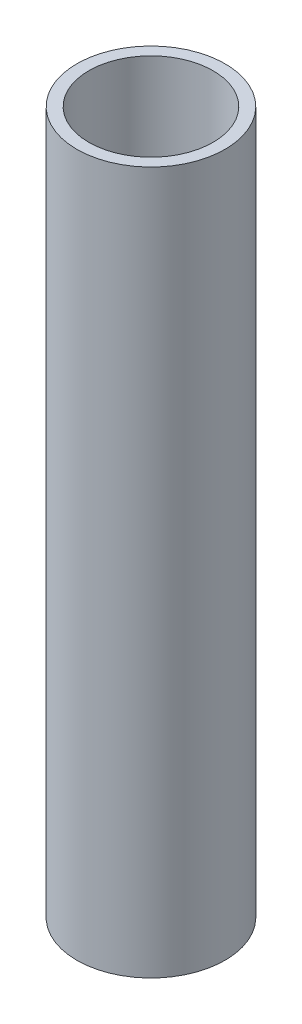
SolidWorks part; units mm, degrees
material "PVC Rigid"
ref_plane "Front Plane" through (0, 0, 0) normal (0, 0, 1) x (1, 0, 0)
ref_plane "Top Plane" through (0, 0, 0) normal (0, 1, 0) x (1, 0, 0)
ref_plane "Right Plane" through (0, 0, 0) normal (1, 0, 0) x (0, 0, -1)
sketch "Sketch1" plane through (0, 0, 0) normal (0, 1, 0) x (1, 0, 0)
  circle A0 centre (0, 0) radius 24.13
  circle A1 centre (0, 0) radius 20.2184
  point P3 (0, 0)
  dimension "D1" = 48.26
  dimension "D2" = 3.9116
extrude "Boss-Extrude1" add sketch "Sketch1" against normal blind 228.6
